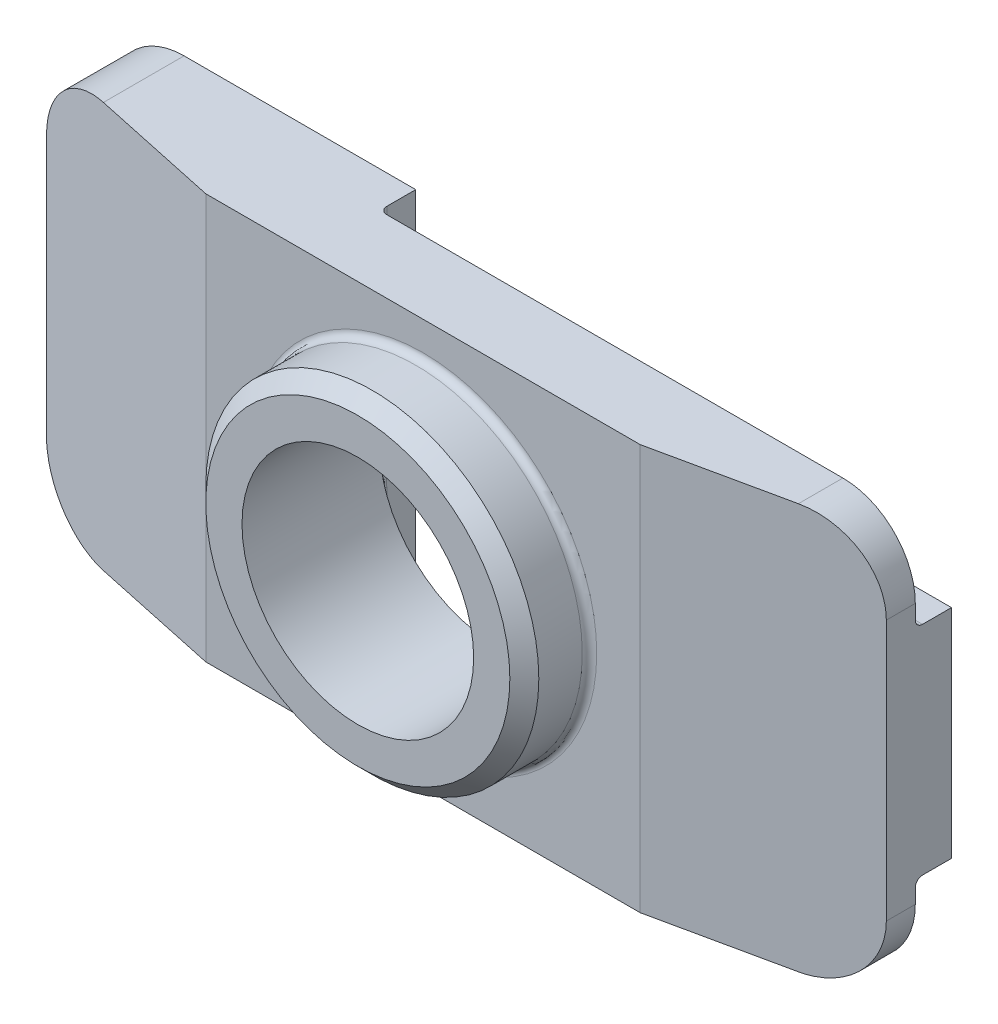
SolidWorks part; units mm, degrees
material "6061 Alloy"
ref_plane "Front Plane" through (0, 0, 0) normal (0, 0, 1) x (1, 0, 0)
ref_plane "Top Plane" through (0, 0, 0) normal (0, 1, 0) x (1, 0, 0)
ref_plane "Right Plane" through (0, 0, 0) normal (1, 0, 0) x (0, 0, -1)
sketch "Sketch2" plane through (0, 0, 0) normal (0, 0, 1) x (1, 0, 0)
  line L1 (-29, -14) -> (29, -14)
  line L2 (-29, -14) -> (-29, 14)
  line L3 (-29, 14) -> (29, 14)
  line L4 (29, -14) -> (29, 14)
  circle A1 centre (0, 0) radius 8
  dimension "D5" = 16
  dimension "D1" = 28
  dimension "D2" = 29
  dimension "D3" = 58
  dimension "D4" = 14
extrude "Boss-Extrude1" add sketch "Sketch2" along normal blind 5
sketch "Sketch3" plane through (0, 0, 5) normal (0, 0, 1) x (1, 0, 0)
  circle A0 centre (0, 0) radius 8
  circle A1 centre (0, 0) radius 11.5
  dimension "D1" = 23
  dimension "D2" = 16
extrude "Boss-Extrude2" add sketch "Sketch3" along normal blind 4.5
sketch "Sketch5" plane through (0, 0, 0) normal (0, 0, -1) x (-1, 0, 0)
  line L0 (-29, 7.5) -> (-10, 7.5)
  line L1 (-29, -14) -> (-29, 14) construction
  line L2 (-10, 7.5) -> (-10, -7.5)
  line L3 (-10, -7.5) -> (-29, -7.5)
  line L4 (-29, 14) -> (29, 14) construction
  line L6 (0, 0) -> (0, 17.1376) construction
  line L11 (29, -14) -> (29, 14)
  line L12 (29, 14) -> (-29, 14)
  line L13 (-29, 14) -> (-29, -14)
  line L14 (-29, -14) -> (29, -14)
  line L17 (-29, 7.5) -> (-29, -7.5)
  dimension "D1" = 15
  dimension "D2" = 6.5
  dimension "D3" = 10
  dimension "D4" = 0
extrude "Boss-Extrude3" add sketch "Sketch5" along normal blind 3
sketch "Sketch6" plane through (0, 0, 0) normal (0, 0, -1) x (-1, 0, 0)
  line L0 (29, -14) -> (-29, -14) construction
  line L1 (29, 14) -> (9.5, 14)
  line L2 (29, 14) -> (29, 7.75)
  line L3 (29, 7.75) -> (9.5, 7.75)
  line L4 (9.5, 14) -> (9.5, 7.75)
  line L5 (9.5, 14) -> (8, 14)
  line L6 (9.5, 14) -> (9.5, -14)
  line L7 (9.5, -14) -> (8, -14)
  line L8 (8, 14) -> (8, -14)
  line L10 (29, -14) -> (9.5, -14)
  line L11 (29, -14) -> (29, -7.75)
  line L12 (29, -7.75) -> (9.5, -7.75)
  line L13 (9.5, -14) -> (9.5, -7.75)
  line M11 (-29, -14) -> (29, -14)
  line M12 (29, -14) -> (29, 14)
  line M13 (29, 14) -> (-29, 14)
  dimension "D1" = 8
  dimension "D2" = 1.5
  dimension "D3" = 6.25
  dimension "D4" = 6.25
extrude "Boss-Extrude4" add sketch "Sketch6" along normal blind 2.5 contours L8 L6 L4 M13 M11 | L4 L3 M13 M12 | L12 L6 M12 M11 region at (-19.25, 10.875, 0) region at (-8.75, 0, 0) region at (-19.25, -10.875, 0)
fillet "Fillet2" radius 0.5 1 edges at (-11.5, 0, 5)
chamfer "Chamfer1" distance 2 angle 45 2 edges at (10, -7.5, -1.5) (10, 7.5, -1.5)
fillet "Fillet3" radius 1.8 2 edges at (-9.5, 7.75, -1.25) (-9.5, -7.75, -1.25)
fillet "Fillet6" radius 0.5 5 edges at (20.5, 7.5, 0) (11, 6.5, 0) (10, 0, 0) (11, -6.5, 0) (20.5, -7.5, 0)
fillet "Fillet7" radius 0.5 2 edges at (-8, -7, 0) (-8, 7, 0)
fillet "Fillet8" radius 0.5 5 edges at (-20.15, -7.75, 0) (-10.0272, -7.2228, 0) (-10.0272, 7.2228, 0) (-9.5, 0, 0) (-20.15, 7.75, 0)
sketch "Sketch7" plane through (0, 0, -3) normal (0, 0, -1) x (-1, 0, 0)
  line L0 (-29, 0) -> (15.2791, 0) construction
  line L1 (-29, 7.5) -> (-29, -7.5) construction
  line L2 (-10, -5.5) -> (-10, 5.5) construction
  line L4 (-30.745, 9.35) -> (-8.4238, 9.35)
  line L5 (-30.745, 9.35) -> (-30.745, -9.6947)
  line L6 (-30.745, -9.6947) -> (-8.4238, -9.6947)
  line L7 (-8.4238, 9.35) -> (-8.4238, -9.6947)
  circle A0 centre (-16, 0) radius 4.75
  dimension "D2" = 9.5
  dimension "D1" = 6
extrude "Cut-Extrude1" cut sketch "Sketch7" against normal blind 0.5
chamfer "Chamfer3" distance 3 distance2 14 2 edges at (29, 0, 5) (-29, 0, 5) first distance on face at (29, 0, 0.4207) first distance on face at (-29, 0, -0.0793)
fillet "Fillet4" radius 5 4 edges at (29, -14, 1) (-29, -14, -0.25) (-29, 14, -0.25) (29, 14, 1)
chamfer "Chamfer4" distance 1 angle 45 1 edges at (11.5, 0, 9.5)
fillet "Fillet9" radius 0.5 1 edges at (11.25, 0, -2.5)
